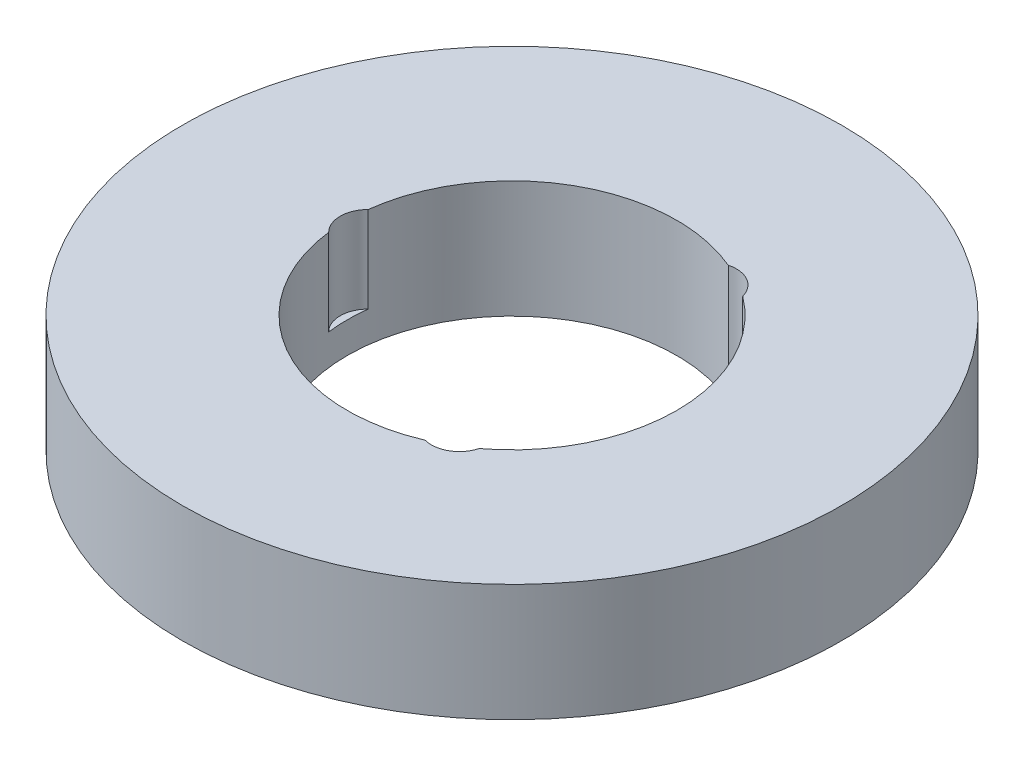
SolidWorks part; units mm, degrees
ref_plane "Front Plane" through (0, 0, 0) normal (0, 0, 1) x (1, 0, 0)
ref_plane "Top Plane" through (0, 0, 0) normal (0, 1, 0) x (1, 0, 0)
ref_plane "Right Plane" through (0, 0, 0) normal (1, 0, 0) x (0, 0, -1)
sketch "Sketch1" plane through (0, 0, 0) normal (0, 1, 0) x (1, 0, 0)
  circle A0 centre (0, 0) radius 45
  dimension "FLANGE_OD" = 90
extrude "Boss-Extrude1" add sketch "Sketch1" along normal blind 16
sketch "Sketch2" plane through (0, 0, 0) normal (0, 1, 0) x (1, 0, 0)
  circle A0 centre (0, 0) radius 22.5
  dimension "BORE_D" = 45
extrude "Cut-Extrude1" cut sketch "Sketch2" along normal through all
sketch "Sketch3" plane through (0, 16, 0) normal (0, 1, 0) x (1, 0, 0)
  circle A0 centre (0, 0) radius 19.6489 construction
  circle A1 centre (-19.6489, 0) radius 3.806
  dimension "BOLT_D" = 7.6121
  dimension "BOLT_PCD" = 39.2978
extrude "Cut-Extrude2" cut sketch "Sketch3" against normal blind 11.7744
pattern_circular "CirPattern1" count 3 over 360 about axis through (0, 0, 0) along (0, 1, 0) of "Cut-Extrude2"
